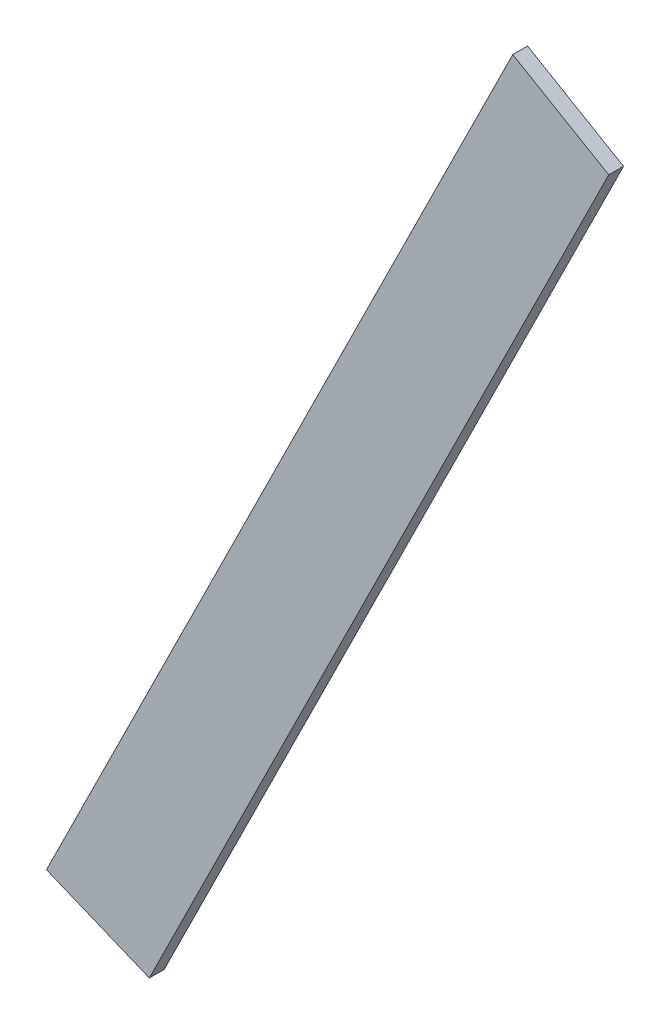
SolidWorks part; units mm, degrees
ref_plane "Front Plane" through (0, 0, 0) normal (0, 0, 1) x (1, 0, 0)
ref_plane "Top Plane" through (0, 0, 0) normal (0, 1, 0) x (1, 0, 0)
ref_plane "Right Plane" through (0, 0, 0) normal (1, 0, 0) x (0, 0, -1)
sketch "Sketch1" plane through (0, 0, 0) normal (0, 0, 1) x (1, 0, 0)
  line L0 (31.4375, -12.7276) -> (17.53, -7.0085)
  line L2 (17.53, -7.0085) -> (80.5702, 119.956)
  line L4 (31.4375, -12.7276) -> (93.5449, 112.3579)
  line L5 (93.5449, 112.3579) -> (80.5702, 119.956)
  line L6 (152.5656, 77.7948) -> (-20.019, 178.8619) construction
  line L7 (-90.1599, 37.2762) -> (94.8109, -38.7882) construction
  dimension "D1" = 15
extrude "Boss-Extrude1" add sketch "Sketch1" along normal blind 2
ref_plane "Plane1" through (23.5721, -11.704, 0) normal (0.8957, -0.4447, 0) x (0, 0, -1)
